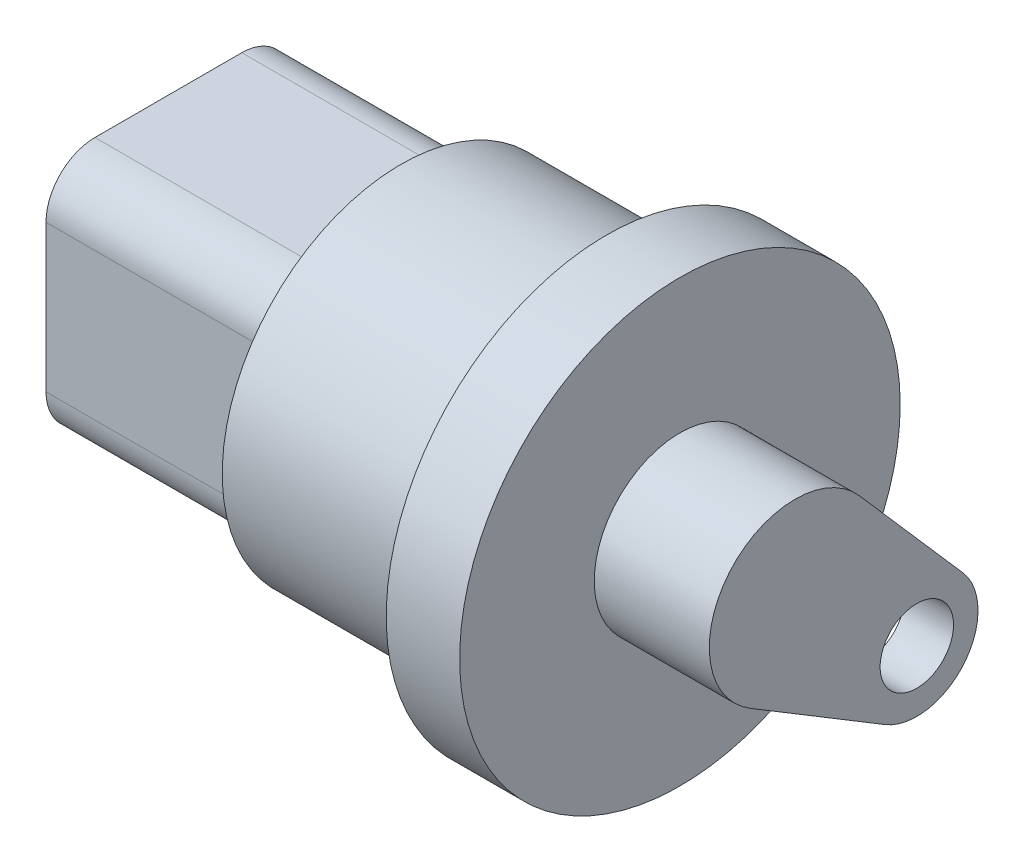
SolidWorks part; units mm, degrees
ref_plane "Front Plane" through (0, 0, 0) normal (0, 0, 1) x (1, 0, 0)
ref_plane "Top Plane" through (0, 0, 0) normal (0, 1, 0) x (1, 0, 0)
ref_plane "Right Plane" through (0, 0, 0) normal (1, 0, 0) x (0, 0, -1)
sketch "Sketch2" plane through (0, 0, 0) normal (1, 0, 0) x (0, 0, -1)
  line L1 (-5, 5) -> (5, 5)
  line L2 (-5, 5) -> (-5, -5)
  line L3 (-5, -5) -> (5, -5)
  line L4 (5, 5) -> (5, -5)
  line L5 (-5, 5) -> (5, -5) construction
  line L6 (-5, -5) -> (5, 5) construction
  circle A0 centre (0, 0) radius 7.3
  circle A1 centre (0, 0) radius 9
  dimension "D1" = 14.6
  dimension "D4" = 18
  dimension "D2" = 10
  dimension "D3" = 10
extrude "Boss-Extrude1" add sketch "Sketch2" along normal blind 3 contours A1
extrude "Boss-Extrude2" add sketch "Sketch2<4>" against normal blind 8.4 contours A0
sketch "Sketch2<4>" plane through (0, 0, 0) normal (1, 0, 0) x (0, 0, -1) same geometry as "Sketch2"
extrude "Boss-Extrude3" add sketch "Sketch2<6>" against normal blind 9.5 from surface contours L4 L3 L2 L1 starting at face at (-8.4, 0, -7.3)
sketch "Sketch2<6>" plane through (0, 0, 0) normal (1, 0, 0) x (0, 0, -1) same geometry as "Sketch2"
sketch "Sketch6" plane through (0, 0, 0) normal (1, 0, 0) x (0, 0, -1)
  line L0 (-5, -5) -> (5, 5) construction
  line L1 (0, 0) -> (8.6111, -7.2256) construction
  line L2 (2.6355, 2.3031) -> (6.8618, -2.533)
  line L4 (-1.8105, -2.9954) -> (3.6861, -6.3177)
  line L5 (0, 0) -> (0, -13.1884)
  circle A0 centre (4.9793, -4.1781) radius 2.5
  circle A1 centre (0, 0) radius 9
  circle A2 centre (0, 0) radius 9 construction
  circle A3 centre (0, 0) radius 3.5
  circle A4 centre (4.9793, -4.1781) radius 1.5
  point P12 (3.9618, -4.7215)
  dimension "D2" = 5
  dimension "D3" = 7
  dimension "D4" = 3
  dimension "D1" = 50
extrude "Boss-Extrude6" add sketch "Sketch6" along normal blind 2.7 from surface contours A3 starting at face at (3, 0, -9)
extrude "Boss-Extrude7" add sketch "Sketch6<4>" along normal blind 2 from surface contours A0 L1 A4 | L1 A0 A4 | A3 L1 A0 L2 | L1 A3 L5 L4 A0 | L5 L1 A3 | A3 L4 L5 | L1 L5 A3 region at (0, 0.3304, 0.1541) region at (0, -2.0483, -0.9551) region at (0, -0.8446, -4.2128) region at (0, -4.0309, -1.7198) region at (0, -3.6287, 0.4664) region at (0, -1.7385, -4.9548) region at (0, -2.9387, -3.4084) starting at face at (5.7, 0, -3.5)
sketch "Sketch6<4>" plane through (0, 0, 0) normal (1, 0, 0) x (0, 0, -1) same geometry as "Sketch6"
extrude "Cut-Extrude1" cut sketch "Sketch6<5>" against normal up to surface from surface contours A4 L1 | L1 A4 region at (0, -3.6904, -5.3885) region at (0, -4.6658, -4.5701) up to face at (0, 0, -7.3) starting at face at (3, 0, -3.5)
sketch "Sketch6<5>" plane through (0, 0, 0) normal (1, 0, 0) x (0, 0, -1) same geometry as "Sketch6"
fillet "Fillet1" radius 2 4 edges at (-13.15, 5, 5) (-13.15, -5, 5) (-13.15, -5, -5) (-13.15, 5, -5)
